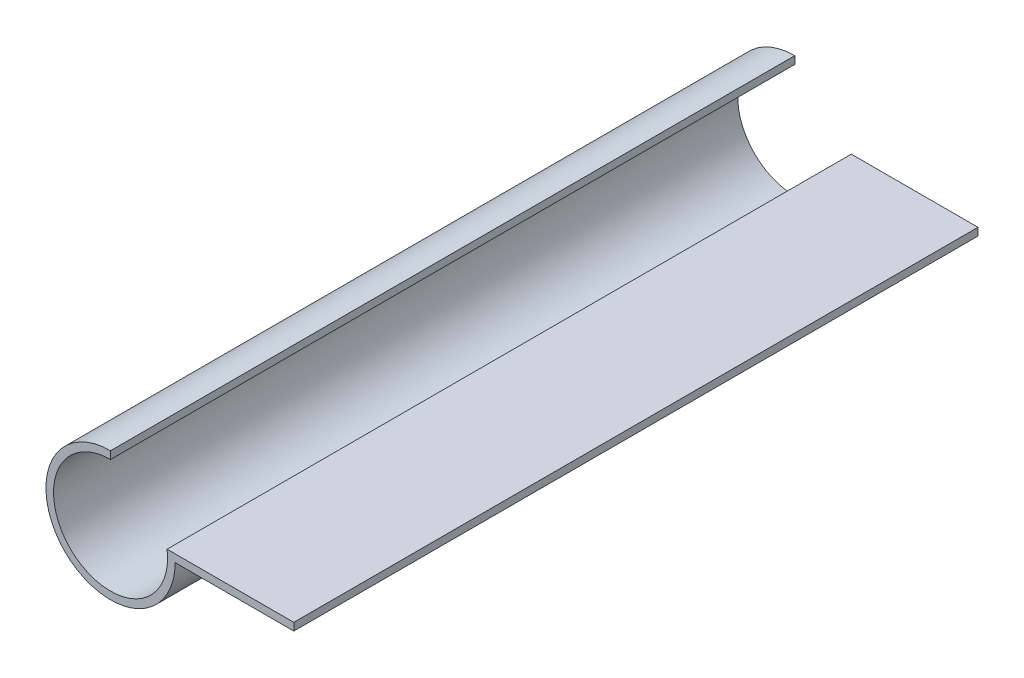
SolidWorks part; units mm, degrees
ref_plane "Front Plane" through (0, 0, 0) normal (0, 0, 1) x (1, 0, 0)
ref_plane "Top Plane" through (0, 0, 0) normal (0, 1, 0) x (1, 0, 0)
ref_plane "Right Plane" through (0, 0, 0) normal (1, 0, 0) x (0, 0, -1)
sketch "Sketch1" plane through (0, 0, 0) normal (0, 0, 1) x (1, 0, 0)
  line L0 (7.2299, 0) -> (2.55, 0)
  line L1 (7.2299, 0) -> (7.2299, 0.3)
  line L2 (7.2299, 0.3) -> (2.2299, 0.3)
  line L3 (0, 2.25) -> (0, 2.55)
  arc A0 (0, 2.25) -> (2.2299, 0.3) centre (0, 0) ccw
  arc A1 (0, 2.55) -> (2.55, 0) centre (0, 0) ccw
  circle A2 centre (0, 0) radius 2.55 construction
  circle A3 centre (0, 0) radius 2.25 construction
  dimension "D1" = 4.5
  dimension "D3" = 5
  dimension "D4" = 0.3
  dimension "D2" = 0.3
extrude "Boss-Extrude1" add sketch "Sketch1" along normal blind 27 contours A0 L2 L1 L0 A1 L3
equation "\"motorDia\"= 4.5"
equation "\"Width\"= 27mm"
equation "\"D1@Sketch1\"=\"motorDia\""
equation "\"D1@Boss-Extrude1\"=\"Width\""
